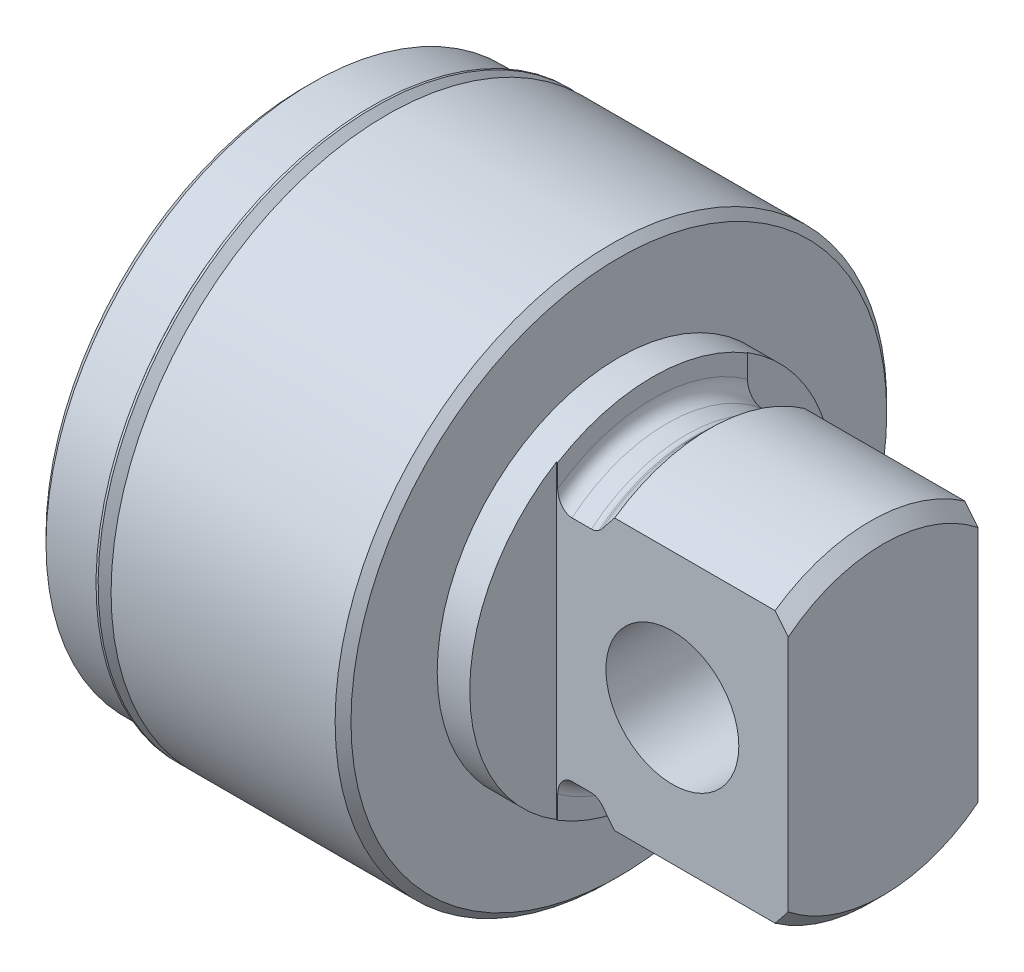
SolidWorks part; units mm, degrees
material "AISI 1045 Steel, cold drawn"
ref_plane "Front Plane" through (0, 0, 0) normal (0, 0, 1) x (1, 0, 0)
ref_plane "Top Plane" through (0, 0, 0) normal (0, 1, 0) x (1, 0, 0)
ref_plane "Right Plane" through (0, 0, 0) normal (1, 0, 0) x (0, 0, -1)
ref_plane "Plane1" through (55.5752, 0, 0) normal (1, 0, 0) x (0, 0, -1)
sketch "Sketch1" plane through (0, 0, 0) normal (0, 0, 1) x (1, 0, 0)
  line L0 (0, 0) -> (0, 24.8095)
  line L1 (0, 24.8095) -> (0.762, 25.5714)
  line L2 (0.762, 25.5714) -> (5.8166, 25.5714)
  line L3 (5.8166, 25.5714) -> (6.8707, 24.5174)
  line L4 (6.8707, 24.5174) -> (7.9248, 24.5174)
  line L5 (7.9248, 24.5174) -> (7.9248, 26.4858)
  line L6 (7.9248, 26.4858) -> (29.4386, 26.4858)
  line L7 (29.4386, 26.4858) -> (30.2006, 25.7238)
  line L8 (30.2006, 25.7238) -> (30.2006, 0)
  line L9 (30.2006, 0) -> (0, 0)
  line L10 (30.2006, 0) -> (0, 0) construction
revolve "Revolve1" add sketch "Sketch1" angle 360 about L10 reverse direction yes
sketch "Sketch2" plane through (0, 0, 0) normal (0, 0, 1) x (1, 0, 0)
  line L0 (30.2006, 0) -> (30.2006, 17.4434)
  line L1 (30.2006, 17.4434) -> (33.4391, 17.4434)
  line L2 (33.4391, 17.4434) -> (33.4391, 15.6274)
  line L3 (34.8107, 14.2558) -> (36.6776, 14.2558)
  line L4 (37.4015, 14.4623) -> (37.6475, 14.6152)
  line L5 (37.6475, 14.6152) -> (38.9073, 15.875)
  line L6 (38.9073, 15.875) -> (54.3154, 15.875)
  line L7 (54.3154, 15.875) -> (55.5752, 14.6152)
  line L8 (55.5752, 14.6152) -> (55.5752, 0)
  line L9 (55.5752, 0) -> (30.2006, 0)
  line L10 (55.5752, 0) -> (30.2006, 0) construction
  arc A0 (33.4391, 15.6274) -> (34.8107, 14.2558) centre (34.8107, 15.6274) ccw
  arc A1 (36.6776, 14.2558) -> (37.4015, 14.4623) centre (36.6776, 15.6274) ccw
revolve "Revolve2" add sketch "Sketch2" angle 360 about L10 reverse direction yes
cosmetic thread "Cosmetic Thread1" parameters "D1"=17.9277, "D2"=29.2303
sketch "Sketch3" plane through (55.5752, 0, 0) normal (1, 0, 0) x (0, 0, -1)
  line L0 (-52.9717, -105.9434) -> (52.9717, -105.9434)
  line L1 (52.9717, -105.9434) -> (52.9717, 105.9434)
  line L2 (52.9717, 105.9434) -> (-52.9717, 105.9434)
  line L3 (-52.9717, 105.9434) -> (-52.9717, -105.9434)
  line L4 (-9.1123, -52.9717) -> (9.1123, -52.9717)
  line L5 (9.1123, -52.9717) -> (9.1123, 52.9717)
  line L6 (9.1123, 52.9717) -> (-9.1123, 52.9717)
  line L7 (-9.1123, 52.9717) -> (-9.1123, -52.9717)
extrude "Cut-Extrude1" cut sketch "Sketch3" against normal blind 22.2504
ref_plane "Plane2" through (30.2006, 0, 0) normal (1, 0, 0) x (0, 0, -1)
ref_plane "Plane3" through (0, 0, 0) normal (0, 0.9998, 0.0175) x (1, 0, 0)
ref_plane "Plane4" through (18.2626, 0, 0) normal (1, 0, 0) x (0, 0, -1)
ref_plane "Plane5" through (6.8707, 0, 0) normal (1, 0, 0) x (0, 0, -1)
sketch "Sketch4" plane through (0, 0, 0) normal (0, 0, 1) x (1, 0, 0)
  line L0 (6.4771, 26.4017) -> (7.7898, 25.089)
  line L1 (7.7898, 24.9094) -> (7.3978, 24.5174)
  line L2 (7.3978, 24.5174) -> (6.8707, 24.5174)
  line L3 (6.8707, 24.5174) -> (6.8707, 24.2634)
  line L4 (6.8707, 24.2634) -> (7.9248, 24.2633)
  line L5 (7.9248, 24.2633) -> (7.9248, 25.2413)
  line L6 (7.9248, 25.2413) -> (6.6803, 26.4858)
  line L7 (6.6803, 26.4858) -> (6.4771, 26.4858)
  line L8 (6.4771, 26.4858) -> (6.4771, 26.4017)
  line L9 (7.9248, 0) -> (6.8707, 0) construction
  arc A0 (7.7898, 25.089) -> (7.7898, 24.9094) centre (7.7, 24.9992) cw
revolve "Revolve3" add sketch "Sketch4" angle 360 about L9 reverse direction yes
ref_plane "Plane6" through (55.7022, 0, 0) normal (1, 0, 0) x (0, 0, -1)
sketch "Sketch5" plane through (0, 0, 0) normal (0, 0, 1) x (1, 0, 0)
  circle A0 centre (44.45, 0) radius 6.3817
extrude "Cut-Extrude2" cut sketch "Sketch5" along normal blind 13.6684 and the other way blind 13.6684
sketch "Sketch6" plane through (0, 0, 0) normal (0, 0, 1) x (1, 0, 0)
  line L0 (0, 0) -> (0, 20.5994)
  line L1 (0, 20.5994) -> (0.762, 19.8374)
  line L2 (0.762, 19.8374) -> (3.175, 19.8374)
  line L3 (3.175, 19.8374) -> (3.175, 16.5926)
  line L4 (3.175, 16.5926) -> (3.937, 15.8306)
  line L5 (3.937, 15.8306) -> (12.7, 15.8306)
  line L6 (12.7, 15.8306) -> (12.7, 0)
  line L7 (12.7, 0) -> (0, 0)
  line L8 (12.7, 0) -> (0, 0) construction
revolve "Cut-Revolve1" cut sketch "Sketch6" angle 360 about L8 reverse direction yes
ref_plane "Plane7" through (33.4391, 0, 0) normal (1, 0, 0) x (0, 0, -1)
ref_plane "Plane8" through (47.6504, 0, 0) normal (1, 0, 0) x (0, 0, -1)
ref_plane "Plane9" through (44.45, 0, 0) normal (1, 0, 0) x (0, 0, -1)
ref_plane "Plane10" through (55.5752, 0, 0) normal (1, 0, 0) x (0, 0, -1)
ref_plane "Plane11" through (0, 0, 0) normal (0, 0, 1) x (1, 0, 0)
ref_plane "Plane12" through (33.4391, 0, 0) normal (1, 0, 0) x (0, 0, -1)
ref_plane "Plane13" through (0, 0, 0) normal (0, 1, 0) x (1, 0, 0)
ref_plane "Plane14" through (0, 0.1016, 0) normal (0, 1, 0) x (1, 0, 0)
ref_plane "Plane15" through (30.2006, 0, 0) normal (1, 0, 0) x (0, 0, -1)
ref_plane "1 XY" through (33.4391, 0, 0) normal (1, 0, 0) x (0, 0, -1)
ref_plane "1 XZ" through (0, 0, 0) normal (0, -1, 0) x (-1, 0, 0)
ref_plane "1 YZ" through (0, 0, 0) normal (0, 0, -1) x (-1, 0, 0)
ref_axis "1 X" through (33.4391, 0, 80.9) along (0, 0, -1)
ref_axis "1 Y" through (33.4391, -50, 0) along (0, 1, 0)
ref_axis "1 Z" through (80.9, 0, 0) along (-1, 0, 0)
sketch3d "1"
  point P0 (33.4391, 0, 0)
ref_plane "c1 XY" through (0, 0, 0) normal (0, 0, 1) x (1, 0, 0)
ref_plane "c1 XZ" through (0, 17.4434, 0) normal (0, -1, 0) x (-1, 0, 0)
ref_plane "c1 YZ" through (30.2006, 0, 0) normal (1, 0, 0) x (0, 0, -1)
ref_axis "c1 X" through (-80.9, 17.4434, 0) along (1, 0, 0)
ref_axis "c1 Y" through (30.2006, -50, 0) along (0, 1, 0)
ref_axis "c1 Z" through (30.2006, 17.4434, 80.9) along (0, 0, -1)
sketch3d "c1"
  point P0 (30.2006, 17.4434, 0)
ref_plane "c2 XY" through (0, 0, 0) normal (0, 0, 1) x (1, 0, 0)
ref_plane "c2 XZ" through (0, -17.4434, 0) normal (0, -1, 0) x (-1, 0, 0)
ref_plane "c2 YZ" through (30.2006, 0, 0) normal (1, 0, 0) x (0, 0, -1)
ref_axis "c2 X" through (-80.9, -17.4434, 0) along (1, 0, 0)
ref_axis "c2 Y" through (30.2006, -50, 0) along (0, 1, 0)
ref_axis "c2 Z" through (30.2006, -17.4434, 80.9) along (0, 0, -1)
sketch3d "c2"
  point P0 (30.2006, -17.4434, 0)
ref_plane "cc1 XY" through (0, 0, 0) normal (0, 0, 1) x (1, 0, 0)
ref_plane "cc1 XZ" through (0, 0, 0) normal (0, -1, 0) x (-1, 0, 0)
ref_plane "cc1 YZ" through (30.2006, 0, 0) normal (1, 0, 0) x (0, 0, -1)
ref_axis "cc1 X" through (-80.9, 0, 0) along (1, 0, 0)
ref_axis "cc1 Y" through (30.2006, -50, 0) along (0, 1, 0)
ref_axis "cc1 Z" through (30.2006, 0, 80.9) along (0, 0, -1)
sketch3d "cc1"
  point P0 (30.2006, 0, 0)
ref_plane "cc2 XY" through (0, 0, 0) normal (0, 0, 1) x (1, 0, 0)
ref_plane "cc2 XZ" through (0, 0, 0) normal (0, -1, 0) x (-1, 0, 0)
ref_plane "cc2 YZ" through (33.4391, 0, 0) normal (1, 0, 0) x (0, 0, -1)
ref_axis "cc2 X" through (-80.9, 0, 0) along (1, 0, 0)
ref_axis "cc2 Y" through (33.4391, -50, 0) along (0, 1, 0)
ref_axis "cc2 Z" through (33.4391, 0, 80.9) along (0, 0, -1)
sketch3d "cc2"
  point P0 (33.4391, 0, 0)
ref_plane "lovra1 XY" through (47.6504, 0, 0) normal (1, 0, 0) x (0, 0, -1)
ref_plane "lovra1 XZ" through (0, 0, 0) normal (0, -1, 0) x (-1, 0, 0)
ref_plane "lovra1 YZ" through (0, 0, 0) normal (0, 0, -1) x (-1, 0, 0)
ref_axis "lovra1 X" through (47.6504, 0, 80.9) along (0, 0, -1)
ref_axis "lovra1 Y" through (47.6504, -50, 0) along (0, 1, 0)
ref_axis "lovra1 Z" through (80.9, 0, 0) along (-1, 0, 0)
sketch3d "lovra1"
  point P0 (47.6504, 0, 0)
ref_plane "lovra2 XY" through (47.6504, 0, 0) normal (1, 0, 0) x (0, 0, -1)
ref_plane "lovra2 XZ" through (0, 15.748, 0) normal (0, -1, 0) x (-1, 0, 0)
ref_plane "lovra2 YZ" through (0, 0, 0) normal (0, 0, -1) x (-1, 0, 0)
ref_axis "lovra2 X" through (47.6504, 15.748, 80.9) along (0, 0, -1)
ref_axis "lovra2 Y" through (47.6504, -50, 0) along (0, 1, 0)
ref_axis "lovra2 Z" through (80.9, 15.748, 0) along (-1, 0, 0)
sketch3d "lovra2"
  point P0 (47.6504, 15.748, 0)
ref_plane "lovra21 XY" through (0, 0, 0) normal (1, 0, 0) x (0, 0, -1)
ref_plane "lovra21 XZ" through (0, 0, 0) normal (0, -1, 0) x (-1, 0, 0)
ref_plane "lovra21 YZ" through (0, 0, 5.2705) normal (0, 0, -1) x (-1, 0, 0)
ref_axis "lovra21 X" through (0, 0, 80.9) along (0, 0, -1)
ref_axis "lovra21 Y" through (0, -50, 5.2705) along (0, 1, 0)
ref_axis "lovra21 Z" through (80.9, 0, 5.2705) along (-1, 0, 0)
sketch3d "lovra21"
  point P0 (0, 0, 5.2705)
ref_plane "lovra22 XY" through (0, 0, 0) normal (1, 0, 0) x (0, 0, -1)
ref_plane "lovra22 XZ" through (0, 0, 0) normal (0, -1, 0) x (-1, 0, 0)
ref_plane "lovra22 YZ" through (0, 0, -5.2705) normal (0, 0, -1) x (-1, 0, 0)
ref_axis "lovra22 X" through (0, 0, 80.9) along (0, 0, -1)
ref_axis "lovra22 Y" through (0, -50, -5.2705) along (0, 1, 0)
ref_axis "lovra22 Z" through (80.9, 0, -5.2705) along (-1, 0, 0)
sketch3d "lovra22"
  point P0 (0, 0, -5.2705)
ref_plane "lovra3 XY" through (47.6504, 0, 0) normal (1, 0, 0) x (0, 0, -1)
ref_plane "lovra3 XZ" through (0, -15.748, 0) normal (0, -1, 0) x (-1, 0, 0)
ref_plane "lovra3 YZ" through (0, 0, 0) normal (0, 0, -1) x (-1, 0, 0)
ref_axis "lovra3 X" through (47.6504, -15.748, 80.9) along (0, 0, -1)
ref_axis "lovra3 Y" through (47.6504, -50, 0) along (0, 1, 0)
ref_axis "lovra3 Z" through (80.9, -15.748, 0) along (-1, 0, 0)
sketch3d "lovra3"
  point P0 (47.6504, -15.748, 0)
ref_plane "olen XY" through (44.45, 0, 0) normal (1, 0, 0) x (0, 0, -1)
ref_plane "olen XZ" through (0, 0, 0) normal (0, -1, 0) x (-1, 0, 0)
ref_plane "olen YZ" through (0, 0, 0) normal (0, 0, -1) x (-1, 0, 0)
ref_axis "olen X" through (44.45, 0, 80.9) along (0, 0, -1)
ref_axis "olen Y" through (44.45, -50, 0) along (0, 1, 0)
ref_axis "olen Z" through (80.9, 0, 0) along (-1, 0, 0)
sketch3d "olen"
  point P0 (44.45, 0, 0)
ref_plane "p1 XY" through (55.5752, 0, 0) normal (1, 0, 0) x (0, 0, -1)
ref_plane "p1 XZ" through (0, 0, 0) normal (0, -1, 0) x (-1, 0, 0)
ref_plane "p1 YZ" through (0, 0, 9.525) normal (0, 0, -1) x (-1, 0, 0)
ref_axis "p1 X" through (55.5752, 0, 80.9) along (0, 0, -1)
ref_axis "p1 Y" through (55.5752, -50, 9.525) along (0, 1, 0)
ref_axis "p1 Z" through (80.9, 0, 9.525) along (-1, 0, 0)
sketch3d "p1"
  point P0 (55.5752, 0, 9.525)
ref_plane "p2 XY" through (55.5752, 0, 0) normal (1, 0, 0) x (0, 0, -1)
ref_plane "p2 XZ" through (0, 0, 0) normal (0, -1, 0) x (-1, 0, 0)
ref_plane "p2 YZ" through (0, 0, -9.525) normal (0, 0, -1) x (-1, 0, 0)
ref_axis "p2 X" through (55.5752, 0, 80.9) along (0, 0, -1)
ref_axis "p2 Y" through (55.5752, -50, -9.525) along (0, 1, 0)
ref_axis "p2 Z" through (80.9, 0, -9.525) along (-1, 0, 0)
sketch3d "p2"
  point P0 (55.5752, 0, -9.525)
ref_plane "port XY" through (0, 0, 0) normal (0, 0, 1) x (1, 0, 0)
ref_plane "port XZ" through (0, 0, 0) normal (0, -1, 0) x (-1, 0, 0)
ref_plane "port YZ" through (18.2626, 0, 0) normal (1, 0, 0) x (0, 0, -1)
ref_axis "port X" through (-80.9, 0, 0) along (1, 0, 0)
ref_axis "port Y" through (18.2626, -50, 0) along (0, 1, 0)
ref_axis "port Z" through (18.2626, 0, 80.9) along (0, 0, -1)
sketch3d "port"
  point P0 (18.2626, 0, 0)
ref_plane "port2 XY" through (55.5752, 0, 0) normal (1, 0, 0) x (0, 0, -1)
ref_plane "port2 XZ" through (0, 0, 0) normal (0, -1, 0) x (-1, 0, 0)
ref_plane "port2 YZ" through (0, 0, 0) normal (0, 0, -1) x (-1, 0, 0)
ref_axis "port2 X" through (55.5752, 0, 80.9) along (0, 0, -1)
ref_axis "port2 Y" through (55.5752, -50, 0) along (0, 1, 0)
ref_axis "port2 Z" through (80.9, 0, 0) along (-1, 0, 0)
sketch3d "port2"
  point P0 (55.5752, 0, 0)
ref_plane "thd1 XY" through (55.5752, 0, 0) normal (1, 0, 0) x (0, 0, -1)
ref_plane "thd1 XZ" through (0, 0, 0) normal (0, -1, 0) x (-1, 0, 0)
ref_plane "thd1 YZ" through (0, 0, 15.875) normal (0, 0, -1) x (-1, 0, 0)
ref_axis "thd1 X" through (55.5752, 0, 80.9) along (0, 0, -1)
ref_axis "thd1 Y" through (55.5752, -50, 15.875) along (0, 1, 0)
ref_axis "thd1 Z" through (80.9, 0, 15.875) along (-1, 0, 0)
sketch3d "thd1"
  point P0 (55.5752, 0, 15.875)
ref_plane "thd2 XY" through (55.5752, 0, 0) normal (1, 0, 0) x (0, 0, -1)
ref_plane "thd2 XZ" through (0, 0, 0) normal (0, -1, 0) x (-1, 0, 0)
ref_plane "thd2 YZ" through (0, 0, -15.875) normal (0, 0, -1) x (-1, 0, 0)
ref_axis "thd2 X" through (55.5752, 0, 80.9) along (0, 0, -1)
ref_axis "thd2 Y" through (55.5752, -50, -15.875) along (0, 1, 0)
ref_axis "thd2 Z" through (80.9, 0, -15.875) along (-1, 0, 0)
sketch3d "thd2"
  point P0 (55.5752, 0, -15.875)
ref_plane "to_mounting_bracket XY" through (30.2006, 0, 0) normal (1, 0, 0) x (0, 0, -1)
ref_plane "to_mounting_bracket XZ" through (0, 0, 0) normal (0, -1, 0) x (-1, 0, 0)
ref_plane "to_mounting_bracket YZ" through (0, 0, 0) normal (0, 0, -1) x (-1, 0, 0)
ref_axis "to_mounting_bracket X" through (30.2006, 0, 80.9) along (0, 0, -1)
ref_axis "to_mounting_bracket Y" through (30.2006, -50, 0) along (0, 1, 0)
ref_axis "to_mounting_bracket Z" through (80.9, 0, 0) along (-1, 0, 0)
sketch3d "to_mounting_bracket"
  point P0 (30.2006, 0, 0)
ref_plane "to_nut XY" through (33.4391, 0, 0) normal (1, 0, 0) x (0, 0, -1)
ref_plane "to_nut XZ" through (0, 0, 0) normal (0, -1, 0) x (-1, 0, 0)
ref_plane "to_nut YZ" through (0, 0, 0) normal (0, 0, -1) x (-1, 0, 0)
ref_axis "to_nut X" through (33.4391, 0, 80.9) along (0, 0, -1)
ref_axis "to_nut Y" through (33.4391, -50, 0) along (0, 1, 0)
ref_axis "to_nut Z" through (80.9, 0, 0) along (-1, 0, 0)
sketch3d "to_nut"
  point P0 (33.4391, 0, 0)
ref_plane "to_pin XY" through (0, 0, 0) normal (0, 0, 1) x (1, 0, 0)
ref_plane "to_pin XZ" through (0, 0, 0) normal (0, -1, 0) x (-1, 0, 0)
ref_plane "to_pin YZ" through (44.45, 0, 0) normal (1, 0, 0) x (0, 0, -1)
ref_axis "to_pin X" through (-80.9, 0, 0) along (1, 0, 0)
ref_axis "to_pin Y" through (44.45, -50, 0) along (0, 1, 0)
ref_axis "to_pin Z" through (44.45, 0, 80.9) along (0, 0, -1)
sketch3d "to_pin"
  point P0 (44.45, 0, 0)
ref_plane "to_screw XY" through (0, 0.1016, 0) normal (0, 1, 0) x (1, 0, 0)
ref_plane "to_screw XZ" through (0, 0, -14.1986) normal (0, 0, 1) x (1, 0, 0)
ref_plane "to_screw YZ" through (18.2626, 0, 0) normal (1, 0, 0) x (0, 0, -1)
ref_axis "to_screw X" through (-80.9, 0.1016, -14.1986) along (1, 0, 0)
ref_axis "to_screw Y" through (18.2626, 0.1016, 50) along (0, 0, -1)
ref_axis "to_screw Z" through (18.2626, 50, -14.1986) along (0, -1, 0)
sketch3d "to_screw"
  point P0 (18.2626, 0.1016, -14.1986)
ref_plane "to_tube XY" through (6.8707, 0, 0) normal (1, 0, 0) x (0, 0, -1)
ref_plane "to_tube XZ" through (0, 0, 0) normal (0, -1, 0) x (-1, 0, 0)
ref_plane "to_tube YZ" through (0, 0, 0) normal (0, 0, -1) x (-1, 0, 0)
ref_axis "to_tube X" through (6.8707, 0, 80.9) along (0, 0, -1)
ref_axis "to_tube Y" through (6.8707, -50, 0) along (0, 1, 0)
ref_axis "to_tube Z" through (80.9, 0, 0) along (-1, 0, 0)
sketch3d "to_tube"
  point P0 (6.8707, 0, 0)
